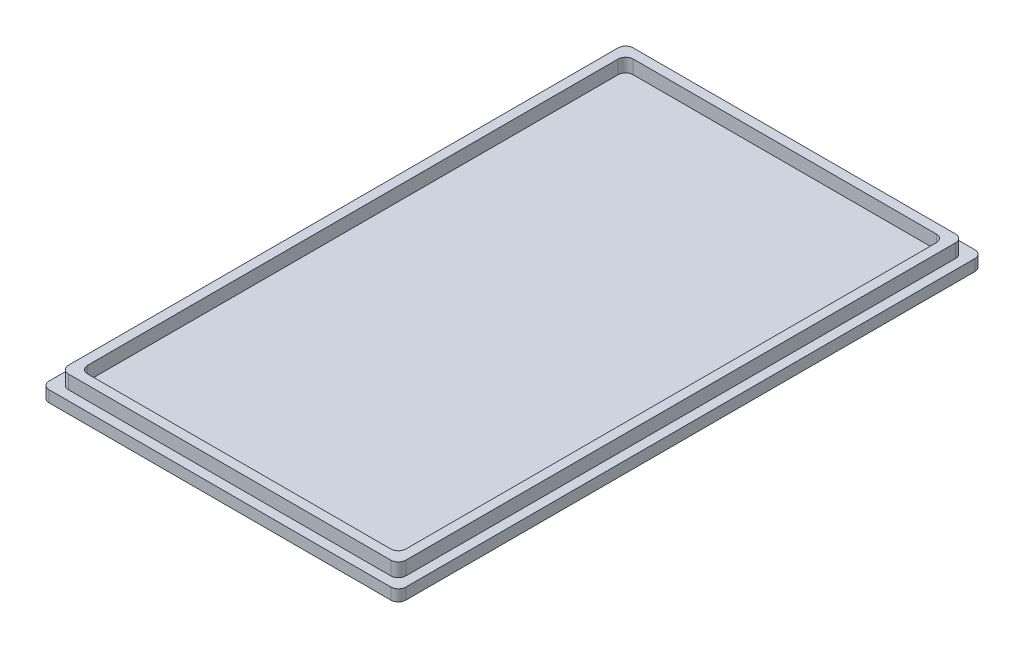
SolidWorks part; units mm, degrees
ref_plane "Front Plane" through (0, 0, 0) normal (0, 0, 1) x (1, 0, 0)
ref_plane "Top Plane" through (0, 0, 0) normal (0, 1, 0) x (1, 0, 0)
ref_plane "Right Plane" through (0, 0, 0) normal (1, 0, 0) x (0, 0, -1)
sketch "Sketch1" plane through (0, 0, 0) normal (0, 1, 0) x (1, 0, 0)
  line L5 (0, 0) -> (47.0912, 0)
  line L6 (0, 0) -> (0, -77.0912)
  line L7 (0, -77.0912) -> (47.0912, -77.0912)
  line L8 (47.0912, 0) -> (47.0912, -77.0912)
extrude "Boss-Extrude1" add sketch "Sketch1" along normal blind 1.5
sketch "Sketch2" plane through (0, 1.5, 0) normal (0, 1, 0) x (1, 0, 0)
  line L3 (1.2728, -1.2728) -> (45.8184, -1.2728)
  line L4 (1.2728, -1.2728) -> (1.2728, -75.8184)
  line L5 (1.2728, -75.8184) -> (45.8184, -75.8184)
  line L6 (45.8184, -1.2728) -> (45.8184, -75.8184)
  line L7 (2.5456, -2.5456) -> (44.5456, -2.5456)
  line L8 (2.5456, -2.5456) -> (2.5456, -74.5456)
  line L9 (2.5456, -74.5456) -> (44.5456, -74.5456)
  line L10 (44.5456, -2.5456) -> (44.5456, -74.5456)
extrude "Boss-Extrude2" add sketch "Sketch2" along normal blind 1.8
fillet "Fillet1" radius 1 12 edges at (2.5456, 2.4, 2.5456) (1.2728, 2.4, 1.2728) (0, 0.75, 0) (2.5456, 2.4, 74.5456) (1.2728, 2.4, 75.8184) (0, 0.75, 77.0912) (44.5456, 2.4, 74.5456) (47.0912, 0.75, 77.0912) (45.8184, 2.4, 75.8184) (44.5456, 2.4, 2.5456) (47.0912, 0.75, 0) (45.8184, 2.4, 1.2728)
